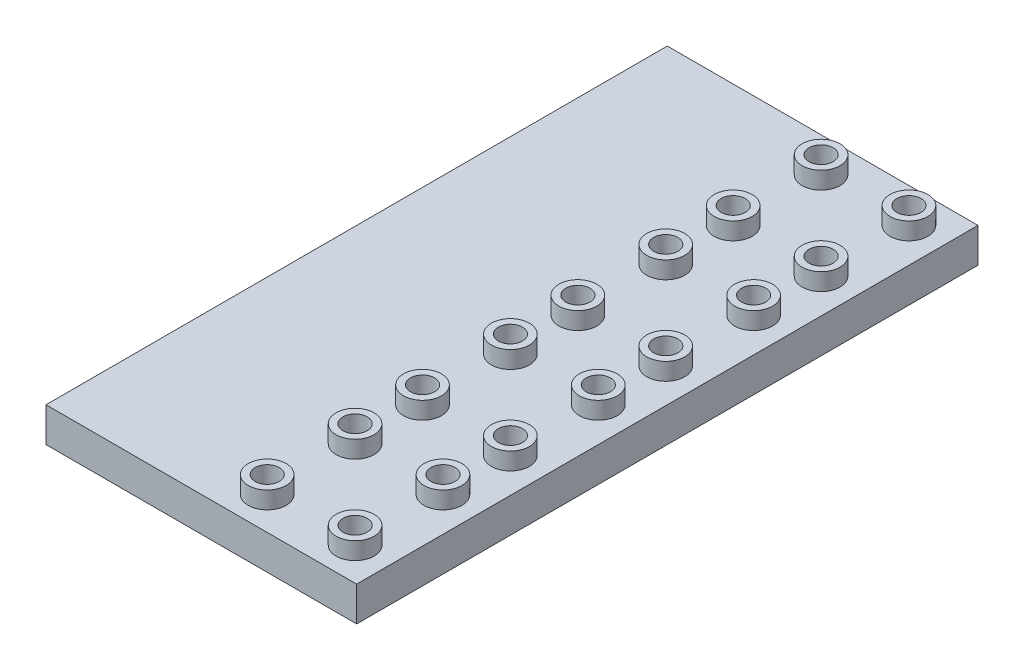
SolidWorks part; units mm, degrees
ref_plane "Front Plane" through (0, 0, 0) normal (0, 0, 1) x (1, 0, 0)
ref_plane "Top Plane" through (0, 0, 0) normal (0, 1, 0) x (1, 0, 0)
ref_plane "Right Plane" through (0, 0, 0) normal (1, 0, 0) x (0, 0, -1)
sketch "Sketch2" plane through (0, 0, 0) normal (0, 1, 0) x (1, 0, 0)
  line L1 (-45, -90) -> (45, -90)
  line L2 (-45, -90) -> (-45, 90)
  line L3 (-45, 90) -> (45, 90)
  line L4 (45, -90) -> (45, 90)
  line L5 (-45, -90) -> (45, 90) construction
  line L6 (-45, 90) -> (45, -90) construction
  circle A0 centre (9.54, 80) radius 5.5
  circle A1 centre (35, 80) radius 5.5
  circle A2 centre (35, 54.54) radius 5.5
  circle A3 centre (9.54, 54.54) radius 5.5
  circle A8 centre (9.54, 80) radius 3.5
  circle A9 centre (35, 54.54) radius 3.5
  circle A10 centre (9.54, 54.54) radius 3.5
  circle A11 centre (35, 80) radius 3.5
  circle A12 centre (9.54, 35) radius 5.5
  circle A13 centre (9.54, 35) radius 3.5
  circle A14 centre (35, 35) radius 3.5
  circle A15 centre (35, 35) radius 5.5
  circle A16 centre (35, 9.54) radius 5.5
  circle A17 centre (35, 9.54) radius 3.5
  circle A18 centre (9.54, 9.54) radius 5.5
  circle A19 centre (9.54, 9.54) radius 3.5
  circle A20 centre (9.54, -10) radius 5.5
  circle A21 centre (9.54, -10) radius 3.5
  circle A22 centre (35, -10) radius 3.5
  circle A23 centre (35, -10) radius 5.5
  circle A24 centre (35, -35.46) radius 5.5
  circle A25 centre (35, -35.46) radius 3.5
  circle A26 centre (9.54, -35.46) radius 5.5
  circle A27 centre (9.54, -35.46) radius 3.5
  circle A28 centre (9.54, -55) radius 5.5
  circle A29 centre (9.54, -55) radius 3.5
  circle A30 centre (35, -55) radius 3.5
  circle A31 centre (35, -55) radius 5.5
  circle A32 centre (35, -80.46) radius 5.5
  circle A33 centre (35, -80.46) radius 3.5
  circle A34 centre (9.54, -80.46) radius 5.5
  circle A35 centre (9.54, -80.46) radius 3.5
  point P0 (0, 0)
  dimension "D3" = 7
  dimension "D1" = 90
  dimension "D2" = 180
  dimension "D4" = 25.46
  dimension "D5" = 25.46
  dimension "D6" = 10
  dimension "D7" = 10
  dimension "D8" = 2
  dimension "D9" = 4
extrude "Boss-Extrude1" add sketch "Sketch2" along normal blind 10 contours L1 L4 L3 L2
extrude "Boss-Extrude2" add sketch "Sketch2<3>" along normal blind 5 from surface contours A34 A35 | A32 A33 | A28 A29 | A31 A30 | A26 A27 | A24 A25 | A20 A21 | A23 A22 | A18 A19 | A16 A17 | A12 A13 | A15 A14 | A3 A10 | A2 A9 | A0 A8 | A1 A11 region at (4.1956, 0, -80) region at (29.6556, 0, -80) region at (29.6556, 0, -54.54) region at (4.1956, 0, -54.54) region at (4.1956, 0, -35) region at (29.6556, 0, -35) region at (29.6556, 0, -9.54) region at (4.1956, 0, -9.54) region at (4.1956, 0, 10) region at (29.6556, 0, 10) region at (29.6556, 0, 35.46) region at (4.1956, 0, 35.46) region at (4.1956, 0, 55) region at (29.6556, 0, 55) region at (29.6556, 0, 80.46) region at (4.1956, 0, 80.46) starting at face at (0, 10, 0)
sketch "Sketch2<3>" plane through (0, 0, 0) normal (0, 1, 0) x (1, 0, 0) same geometry as "Sketch2"
